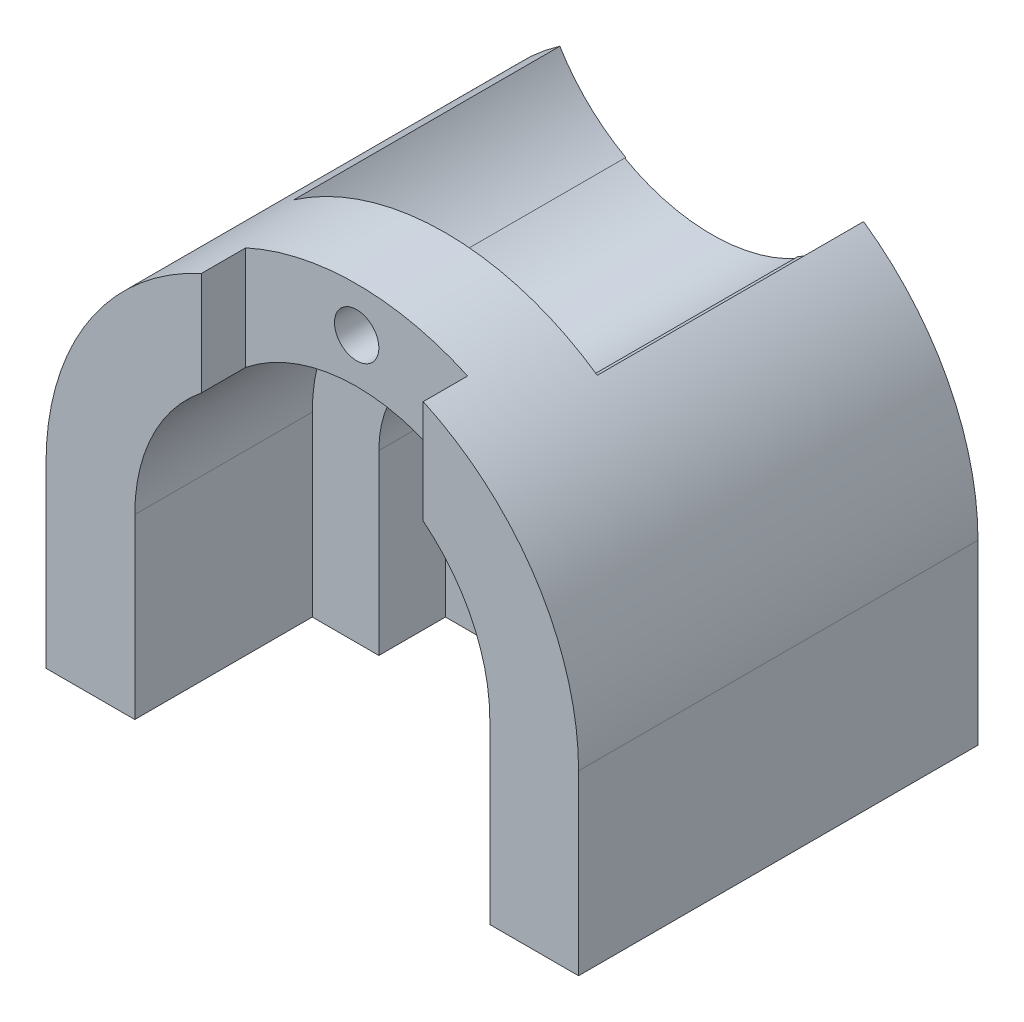
SolidWorks part; units mm, degrees
ref_plane "Front Plane" through (0, 0, 0) normal (0, 0, 1) x (1, 0, 0)
ref_plane "Top Plane" through (0, 0, 0) normal (0, 1, 0) x (1, 0, 0)
ref_plane "Right Plane" through (0, 0, 0) normal (1, 0, 0) x (0, 0, -1)
sketch "Sketch1" plane through (0, 0, 0) normal (0, 0, 1) x (1, 0, 0)
  line L0 (-40, 0) -> (-40, -40)
  line L1 (-40, -40) -> (40, -40)
  line L2 (40, -40) -> (40, 0)
  arc A0 (-40, 0) -> (40, 0) centre (0, 0) cw
  dimension "D1" = 40
  dimension "D2" = 40
extrude "Boss-Extrude1" add sketch "Sketch1" along normal blind 90
sketch "Sketch3" plane through (0, 0, 90) normal (0, 0, 1) x (1, 0, 0)
  circle A0 centre (0, 0) radius 10
  dimension "D1" = 20
  dimension "D2" = 40
  dimension "D3" = 40
extrude "Cut-Extrude2" cut sketch "Sketch3" against normal blind 90
sketch "Sketch6" plane through (0, 0, 90) normal (0, 0, 1) x (1, 0, 0)
  line L0 (-40, 0) -> (-40, -40) construction
  line L1 (-60, 0) -> (-60, -40)
  line L2 (60, 0) -> (60, -40)
  line L3 (60, -40) -> (-60, -40)
  line L4 (-40, -40) -> (40, -40) construction
  arc A0 (-60, 0) -> (60, 0) centre (0, 0) cw
  circle A1 centre (0, 0) radius 10
  dimension "D1" = 20
  dimension "D2" = 20
  dimension "D3" = 0
  dimension "D4" = 40
extrude "Boss-Extrude2" add sketch "Sketch6" against normal blind 90
sketch "Sketch7" plane through (0, 0, 90) normal (0, 0, 1) x (1, 0, 0)
  circle A0 centre (0, 50) radius 5
  dimension "D1" = 10
  dimension "D2" = 0
  dimension "D3" = 90
extrude "Cut-Extrude3" cut sketch "Sketch7" against normal blind 90
sketch "Sketch8" plane through (0, 0, 0) normal (0, 0, -1) x (-1, 0, 0)
  arc A0 (34.2187, 49.2857) -> (-34.2187, 49.2857) centre (0, 70) cw
  arc A1 (60, 0) -> (-60, 0) centre (0, 0) ccw construction
  arc A2 (-34.2187, 49.2857) -> (34.2187, 49.2857) centre (0, 0) cw
  point P6 (0, 60)
  point P7 (0, 60)
  dimension "D3" = 40
  dimension "D1" = 0
  dimension "D2" = 70
extrude "Cut-Extrude4" cut sketch "Sketch8" against normal blind 60
ref_plane "Plane1" through (0, 0, 50) normal (0, 0, 1) x (1, 0, 0)
sketch "Sketch10" plane through (0, 0, 50) normal (0, 0, 1) x (1, 0, 0)
  line L0 (-25, 54.5436) -> (-25, 32)
  line L1 (25, 54.5436) -> (25, 32)
  arc A0 (-25, 54.5436) -> (25, 54.5436) centre (0, 0) cw
  arc A1 (-25, 32) -> (25, 32) centre (0, 0) cw
  dimension "D5" = 60
  dimension "D1" = 25
  dimension "D2" = 25
  dimension "D3" = 32
  dimension "D4" = 32
  dimension "D6" = 0
extrude "Cut-Extrude5" cut sketch "Sketch10" along normal blind 60 contours L0 A1 L1 A0 | L1 A0 L0 A1 region at (0, 47.9522, 50)
ref_plane "Plane2" through (25, 38.775, 50) normal (-0.7806, -0.625, 0) x (0, 0, 1)
sketch "Sketch12" plane through (0, 0, 50) normal (0, 0, 1) x (1, 0, 0)
  line L0 (19.9844, 35.35) -> (25, 32)
  line L1 (25, 32) -> (25, 38.775)
  line L2 (-25, 38.775) -> (-25, 32)
  line L3 (-25, 32) -> (-19.9844, 35.35)
  arc A0 (25, 38.775) -> (19.9844, 35.35) centre (0, 70) cw
  arc A1 (19.9844, 35.35) -> (25, 38.775) centre (0, 70) ccw construction
  arc A2 (-25, 38.775) -> (-19.9844, 35.35) centre (0, 70) ccw
  arc M1 (25, 38.775) -> (19.9844, 35.35) centre (0, 70) cw
  arc M2 (19.9844, 35.35) -> (25, 32) centre (0, 0) cw
  line M3 (25, 32) -> (25, 38.775)
extrude "Boss-Extrude3" add sketch "Sketch12" along normal blind 10 contours M3 M1 M2 | A2 L2 L3 | A2 L2 L3 region at (23.3745, 35.3737, 50) region at (-23.3511, 35.3283, 50)
sketch "Sketch13" plane through (0, 0, 90) normal (0, 0, 1) x (1, 0, 0)
  line L0 (-25, 32) -> (-25, 54.5436)
  line L1 (25, 32) -> (25, 54.5436)
  arc A0 (-25, 32) -> (25, 32) centre (0, 0) cw
  arc A1 (25, 32) -> (-25, 32) centre (0, 0) ccw construction
  arc A2 (-25, 54.5436) -> (25, 54.5436) centre (0, 0) cw
  line M2 (-25, 32) -> (-25, 54.5436)
  line M8 (25, 54.5436) -> (25, 32)
  arc M9 (25, 32) -> (-25, 32) centre (0, 0) ccw
extrude "Boss-Extrude4" add sketch "Sketch13" against normal blind 55 contours A2 M2 M9 M8 region at (0, 47.9522, 90)
sketch "Sketch14" plane through (0, 0, 90) normal (0, 0, 1) x (1, 0, 0)
  line L0 (-25, 54.5436) -> (-25, 32)
  line L1 (25, 54.5436) -> (25, 32)
  arc A0 (-25, 54.5436) -> (25, 54.5436) centre (0, 0) cw
  arc A1 (60, 0) -> (-60, 0) centre (0, 0) ccw construction
  arc A2 (-25, 32) -> (25, 32) centre (0, 0) cw
  arc A4 (19.9844, 35.35) -> (-19.9844, 35.35) centre (0, 0) ccw construction
extrude "Cut-Extrude6" cut sketch "Sketch14" against normal blind 40
sketch "Sketch15" plane through (0, 0, 35) normal (0, 0, -1) x (-1, 0, 0)
  arc A0 (-19.9844, 35.35) -> (19.9844, 35.35) centre (0, 0) cw
  arc A1 (19.9844, 35.35) -> (25, 38.775) centre (0, 70) ccw construction
  arc A2 (-19.9844, 35.35) -> (19.9844, 35.35) centre (0, 70) ccw
  arc A3 (-34.2187, 49.2857) -> (34.2187, 49.2857) centre (0, 70) ccw construction
extrude "Cut-Extrude7" cut sketch "Sketch15" against normal blind 106
sketch "Sketch16" plane through (0, 0, 50) normal (0, 0, 1) x (1, 0, 0)
  circle A0 centre (0, 50) radius 5
  dimension "D1" = 10
  dimension "D2" = 50
extrude "Cut-Extrude8" cut sketch "Sketch16" against normal blind 106
sketch "Sketch17" plane through (0, 0, 90) normal (0, 0, 1) x (1, 0, 0)
  line L0 (-25, 0) -> (-25, -40)
  line L1 (-60, -40) -> (60, -40) construction
  line L2 (25, 0) -> (25, -40)
  line L3 (25, -40) -> (-25, -40)
  arc A0 (-25, 0) -> (25, 0) centre (0, 0) cw
  dimension "D1" = 25
extrude "Cut-Extrude9" cut sketch "Sketch17" against normal blind 70
sketch "Sketch18" plane through (0, 0, 50) normal (0, 0, 1) x (1, 0, 0)
  circle A0 centre (0, 50) radius 5
  dimension "D1" = 10
extrude "Boss-Extrude6" add sketch "Sketch18" against normal blind 15
sketch "Sketch19" plane through (0, 0, 50) normal (0, 0, 1) x (1, 0, 0)
  line L0 (-40, 0) -> (-40, -40)
  line L1 (-40, -40) -> (40, -40)
  line L2 (40, 0) -> (40, -40)
  arc A0 (-40, 0) -> (40, 0) centre (0, 0) cw
  dimension "D1" = 20
  dimension "D2" = 20
  dimension "D3" = 40
  dimension "D4" = 40
  dimension "D5" = 0
  dimension "D6" = 40
extrude "Cut-Extrude18" cut sketch "Sketch19" along normal blind 40
sketch "Sketch22" plane through (-25, 0, 0) normal (1, 0, 0) x (0, 0, -1)
  line L1 (-90, 54.5436) -> (-50, 54.5436)
  line L2 (-90, 54.5436) -> (-90, 12.6996)
  line L3 (-90, 12.6996) -> (-50, 12.6996)
  line L4 (-50, 54.5436) -> (-50, 12.6996)
  dimension "D1" = 0
  dimension "D2" = 41.844
extrude "Cut-Extrude19" cut sketch "Sketch22" along normal blind 20
sketch "Sketch23" plane through (25, 0, 0) normal (-1, 0, 0) x (0, 0, 1)
  line L1 (90, 54.5436) -> (50, 54.5436)
  line L2 (90, 54.5436) -> (90, 14.1759)
  line L3 (90, 14.1759) -> (50, 14.1759)
  line L4 (50, 54.5436) -> (50, 14.1759)
  dimension "D1" = 0
  dimension "D2" = 40.3677
extrude "Cut-Extrude20" cut sketch "Sketch23" along normal blind 20
sketch "Sketch25" plane through (0, 0, 90) normal (0, 0, 1) x (1, 0, 0)
  circle A0 centre (0, 0) radius 25
  dimension "D1" = 50
extrude "Boss-Extrude7" add sketch "Sketch25" against normal blind 40 separate body
sketch "Sketch26" plane through (0, 0, 90) normal (0, 0, 1) x (1, 0, 0)
  circle A0 centre (0, 0) radius 25
  dimension "D1" = 50
extrude "Cut-Extrude21" cut sketch "Sketch26" against normal blind 10
sketch "Sketch27" plane through (0, 0, 35) normal (0, 0, -1) x (-1, 0, 0)
  line L0 (-25, 54.5436) -> (-25, 38.775)
  line L1 (25, 54.5436) -> (25, 38.775)
  line L2 (25, 38.775) -> (25, 54.5436) construction
  arc A0 (-25, 54.5436) -> (25, 54.5436) centre (0, 0) cw
  arc A1 (25, 54.5436) -> (-25, 54.5436) centre (0, 0) ccw construction
  arc A2 (-19.9844, 35.35) -> (19.9844, 35.35) centre (0, 0) cw
  arc A3 (19.9844, 35.35) -> (25, 38.775) centre (0, 70) ccw construction
  arc A4 (25, 38.775) -> (19.9844, 35.35) centre (0, 70) cw
  arc A5 (-25, 38.775) -> (-19.9844, 35.35) centre (0, 70) ccw
  arc A6 (-25, 38.775) -> (-19.9844, 35.35) centre (0, 70) ccw construction
extrude "Cut-Extrude22" cut sketch "Sketch27" against normal blind 34
sketch "Sketch28" plane through (0, 0, 80) normal (0, 0, 1) x (1, 0, 0)
  circle A0 centre (0, 0) radius 25
  dimension "D1" = 50
extrude "Cut-Extrude24" cut sketch "Sketch28" against normal blind 60
sketch "Sketch32" plane through (0, 0, 20) normal (0, 0, 1) x (1, 0, 0)
  line L0 (-25, -40) -> (25, -40)
  line L1 (25, -40) -> (25, 0)
  line L2 (-25, -40) -> (-25, 0)
  arc A0 (25, 0) -> (-25, 0) centre (0, 0) cw
  line M1 (25, -40) -> (25, 0)
  line M3 (-25, 0) -> (-25, -40)
  line M4 (-25, -40) -> (25, -40)
extrude "Boss-Extrude10" add sketch "Sketch32" along normal blind 15 contours A0 M1 M3 M4 region at (0, -29.053, 20)
sketch "Sketch33" plane through (0, 0, 90) normal (0, 0, 1) x (1, 0, 0)
  line L0 (25, 31.225) -> (25, 54.5436) construction
  line L1 (-25, 31.225) -> (-25, 54.5436)
  line L2 (25, 54.5436) -> (25, 31.225)
  arc A0 (-25, 31.225) -> (25, 31.225) centre (0, 0) cw
  arc A1 (40, 0) -> (25, 31.225) centre (0, 0) ccw construction
  arc A2 (-25, 54.5436) -> (25, 54.5436) centre (0, 0) cw
extrude "Boss-Extrude11" add sketch "Sketch33" against normal blind 30
sketch "Sketch34" plane through (0, 0, 50) normal (0, 0, 1) x (1, 0, 0)
  line L0 (-25, 38.775) -> (-25, 31.225)
  arc A0 (-25, 31.225) -> (-19.3649, 35) centre (0, 0) cw
  arc A1 (-25, 38.775) -> (25, 38.775) centre (0, 70) ccw construction
  arc A2 (-25, 38.775) -> (-19.3649, 35) centre (0, 70) ccw
extrude "Cut-Extrude28" cut sketch "Sketch34" along normal blind 209.999
sketch "Sketch35" plane through (0, 0, 90) normal (0, 0, 1) x (1, 0, 0)
  line L0 (-25, 31.225) -> (-25, 38.775)
  arc A0 (-19.3649, 35) -> (-25, 31.225) centre (0, 0) ccw
  arc A1 (-25, 31.225) -> (-40, 0) centre (0, 0) ccw construction
  arc A2 (-25, 38.775) -> (-19.3649, 35) centre (0, 70) ccw
  arc A3 (-25, 38.775) -> (25, 38.775) centre (0, 70) ccw construction
extrude "Boss-Extrude12" add sketch "Sketch35" against normal blind 30
sketch "Sketch36" plane through (0, 0, 0) normal (0, 1, 0) x (1, 0, 0)
  line L1 (25, -90) -> (-25, -90)
  line L2 (25, -90) -> (25, -80)
  line L3 (25, -80) -> (-25, -80)
  line L4 (-25, -90) -> (-25, -80)
  dimension "D1" = 50
  dimension "D2" = 35
  dimension "D3" = 0
  dimension "D4" = 10
extrude "Cut-Extrude29" cut sketch "Sketch36" along normal blind 87
sketch "Sketch38" plane through (0, 0, 80) normal (0, 0, 1) x (1, 0, 0)
  circle A0 centre (0, 50) radius 5
  dimension "D1" = 10
  dimension "D2" = 60
  dimension "50" = 50
extrude "Cut-Extrude30" cut sketch "Sketch38" against normal blind 87
sketch "Sketch39" plane through (0, 0, 0) normal (0, 0, -1) x (-1, 0, 0)
  line L0 (-60, 0) -> (-60, -40)
  line L1 (-60, -40) -> (60, -40)
  line L2 (60, -40) -> (60, 0)
  arc A0 (-34.2187, 49.2857) -> (34.2187, 49.2857) centre (0, 70) ccw
  arc A1 (-34.2187, 49.2857) -> (34.2187, 49.2857) centre (0, 70) ccw construction
  arc A2 (34.2187, 49.2857) -> (60, 0) centre (0, 0) cw
  arc A3 (-34.2187, 49.2857) -> (-60, 0) centre (0, 0) ccw
  circle A4 centre (0, 0) radius 10
  dimension "D1" = 20
extrude "Boss-Extrude14" add sketch "Sketch39" against normal blind 60
sketch "Sketch40" plane through (0, 0, 60) normal (0, 0, 1) x (1, 0, 0)
  line L0 (-25, 0) -> (-25, -40)
  line L1 (40, -40) -> (-40, -40) construction
  line L2 (-25, -40) -> (25, -40)
  line L3 (25, 0) -> (25, -40)
  arc A0 (25, 0) -> (-25, 0) centre (0, 0) ccw
  arc A1 (-25, 0) -> (25, 0) centre (0, 0) ccw
  circle M7 centre (0, 0) radius 10
  dimension "D1" = 25
extrude "Cut-Extrude31" cut sketch "Sketch40" against normal blind 40 contours A0 A1 M7 region at (0, 24.2929, 60)
sketch "Sketch41" plane through (0, 0, 60) normal (0, 0, 1) x (1, 0, 0)
  line L0 (-25, 0) -> (-25, -40)
  line L1 (40, -40) -> (-40, -40) construction
  line L2 (25, 0) -> (25, -40)
  line L3 (25, -40) -> (-25, -40)
  circle A0 centre (0, 0) radius 25 construction
  arc A1 (-25, 0) -> (25, 0) centre (0, 0) ccw
  dimension "D1" = 40
  dimension "D2" = 40
extrude "Cut-Extrude32" cut sketch "Sketch41" against normal blind 20
sketch "Sketch47" plane through (0, 0, 0) normal (0, 1, 0) x (1, 0, 0)
  line L0 (-25, -60) -> (25, -60) construction
  line L1 (-19.2187, -60) -> (20.7813, -60)
  line L2 (-19.2187, -60) -> (-19.2187, -50)
  line L3 (-19.2187, -50) -> (20.7813, -50)
  line L4 (20.7813, -60) -> (20.7813, -50)
  dimension "D1" = 10
  dimension "D2" = 0
  dimension "D3" = 40
  dimension "D4" = 15
extrude "Cut-Extrude34" cut sketch "Sketch47" along normal blind 65
sketch "Sketch48" plane through (0, 0, 60) normal (0, 0, 1) x (1, 0, 0)
  line L0 (-40, 0) -> (-40, -40)
  line L1 (-40, -40) -> (40, -40)
  line L2 (40, -40) -> (40, 0)
  arc A0 (-40, 0) -> (40, 0) centre (0, 0) cw
  arc A1 (40, 0) -> (20.7813, 34.178) centre (0, 0) ccw construction
extrude "Boss-Extrude23" add sketch "Sketch48" along normal blind 20
sketch "Sketch49" plane through (0, 0, 60) normal (0, 0, -1) x (-1, 0, 0)
  circle A0 centre (0, 0) radius 10
  dimension "D1" = 20
extrude "Cut-Extrude35" cut sketch "Sketch49" against normal blind 20
sketch "Sketch50" plane through (0, 0, 80) normal (0, 0, 1) x (1, 0, 0)
  circle A0 centre (0, 0) radius 25
  dimension "D1" = 50
extrude "Cut-Extrude36" cut sketch "Sketch50" against normal blind 60
sketch "Sketch51" plane through (0, 0, 80) normal (0, 0, 1) x (1, 0, 0)
  line L0 (-25, 0) -> (-25, -40)
  line L1 (-40, -40) -> (40, -40) construction
  line L2 (-25, -40) -> (25, -40)
  line L3 (25, -40) -> (25, 0)
  circle A0 centre (0, 0) radius 25 construction
  arc A1 (25, 0) -> (-25, 0) centre (0, 0) cw
  dimension "D1" = 40
  dimension "D2" = 50
  dimension "D3" = 40
extrude "Cut-Extrude39" cut sketch "Sketch51" against normal blind 40
ref_plane "Plane4" through (0, 0, 50) normal (0, 0, 1) x (1, 0, 0)
sketch "Sketch53" plane through (0, 0, 50) normal (0, 0, 1) x (1, 0, 0)
  line L0 (-19.2187, 34.9195) -> (-19.2187, 15.9888)
  line L1 (20.7813, 35.822) -> (20.7813, 13.8974)
  arc A0 (-19.2187, 15.9888) -> (20.7813, 13.8974) centre (0, 0) cw
  arc A1 (20.7813, 13.8974) -> (-19.2187, 15.9888) centre (0, 0) ccw construction
  arc A2 (-19.2187, 34.9195) -> (20.7813, 35.822) centre (0, 70) ccw
  arc A3 (-19.2187, 34.9195) -> (20.7813, 35.822) centre (0, 70) ccw construction
extrude "Cut-Extrude41" cut sketch "Sketch53" along normal blind 4574
sketch "Sketch54" plane through (0, 0, 80) normal (0, 0, 1) x (1, 0, 0)
  line L0 (-25, 0) -> (-25, -40) construction
  line L1 (-25, 0) -> (-25, 31.225)
  line L2 (-25, 54.5436) -> (-25, 31.225) construction
  line L3 (24.9973, -0.366) -> (25, 39.634)
  line L4 (25, 54.5436) -> (25, 31.225) construction
  line L5 (25, 39.634) -> (-25, 39.634)
  line L6 (-25, 39.634) -> (-25, 31.225)
  arc A0 (-25, 0) -> (24.9973, -0.366) centre (0, 0) cw
  arc A1 (-19.2187, 15.9888) -> (-25, 0) centre (0, 0) ccw construction
  arc A2 (25, 0) -> (20.7813, 13.8974) centre (0, 0) ccw construction
  arc A3 (-25, 31.225) -> (-40, 0) centre (0, 0) ccw construction
  arc M2 (-25, 0) -> (-19.2187, 15.9888) centre (0, 0) cw
  line M3 (-19.2187, 15.9888) -> (-19.2187, 34.9195)
  arc M4 (-19.2187, 34.9195) -> (20.7813, 35.822) centre (0, 70) ccw
  line M5 (20.7813, 35.822) -> (20.7813, 13.8974)
  arc M6 (20.7813, 13.8974) -> (25, 0) centre (0, 0) cw
  line M13 (-25, 54.5436) -> (-25, 31.225)
  dimension "D1" = 40
  dimension "D2" = 8.409
extrude "Boss-Extrude24" add sketch "Sketch54" against normal blind 20 contours A0 M3 M5 M4 | L3 L5 L1 M13 M2 M3 M4 M5 M6 region at (-1.0493, 30.3345, 80) region at (1.6305, 26.556, 80)
sketch "Sketch55" plane through (0, 0, 80) normal (0, 0, 1) x (1, 0, 0)
  line L0 (-25, 31.225) -> (-25, 54.5436)
  line L1 (-25, 54.5436) -> (-25, 31.225) construction
  line L2 (25, 31.225) -> (25, 54.5436)
  arc A0 (-20, 35) -> (20, 35) centre (0, 69.641) ccw
  arc A1 (-19.6858, 34.8205) -> (19.6858, 34.8205) centre (0, 0) cw
  arc A3 (-19.2187, 34.9195) -> (20.7813, 35.822) centre (0, 70) ccw construction
  arc A4 (-25, 31.225) -> (25, 31.225) centre (0, 0) cw
  arc A5 (40, 0) -> (25, 31.225) centre (0, 0) ccw construction
  arc A6 (-19.6858, 34.8205) -> (19.6858, 34.8205) centre (0, 0) cw
  arc A7 (25, 54.5436) -> (-25, 54.5436) centre (0, 0) ccw construction
  arc A8 (-25, 54.5436) -> (25, 54.5436) centre (0, 0) cw
  dimension "D5" = 40
  dimension "D1" = 20
  dimension "D2" = 20
  dimension "D3" = 35
  dimension "D4" = 35
extrude "Cut-Extrude43" cut sketch "Sketch55" against normal through all and the other way through all contours A1 A0 region at (0, 34.8205, 80)
sketch "Sketch57" plane through (0, 0, 80) normal (0, 0, 1) x (1, 0, 0)
  line L0 (-40, 0) -> (-40, -40)
  line L1 (-40, -40) -> (-25, -40)
  line L2 (-25, -40) -> (-25, 0)
  line L3 (25, 0) -> (25, -40)
  line L4 (25, -40) -> (40, -40)
  line L5 (25, -40) -> (40, -40) construction
  line L6 (40, -40) -> (40, 0)
  arc A0 (-25, 0) -> (25, 0) centre (0, 0) cw
  arc A1 (25, 0) -> (-25, 0) centre (0, 0) ccw construction
  arc A2 (-40, 0) -> (40, 0) centre (0, 0) cw
  arc A3 (40, 0) -> (25, 31.225) centre (0, 0) ccw construction
  dimension "D1" = 40
extrude "Cut-Extrude47" cut sketch "Sketch57" against normal blind 30
sketch "Sketch60" plane through (0, 0, 40) normal (0, 0, 1) x (1, 0, 0)
  line L0 (-25, -40) -> (25, -40)
  line L1 (25, -40) -> (25, 0)
  line L2 (25, -40) -> (25, 0) construction
  line L3 (-25, -40) -> (-25, 0)
  arc A0 (-25, 0) -> (25, 0) centre (0, 0) ccw construction
  arc A1 (25, 0) -> (-25, 0) centre (0, 0) cw
  arc M1 (25, 0) -> (-25, 0) centre (0, 0) cw
  line M2 (-25, 0) -> (-25, -40)
  line M3 (-25, -40) -> (25, -40)
  line M4 (25, -40) -> (25, 0)
extrude "Cut-Extrude48" cut sketch "Sketch60" against normal blind 5 contours M4 M1 M2 M3 region at (0, -29.053, 40)
